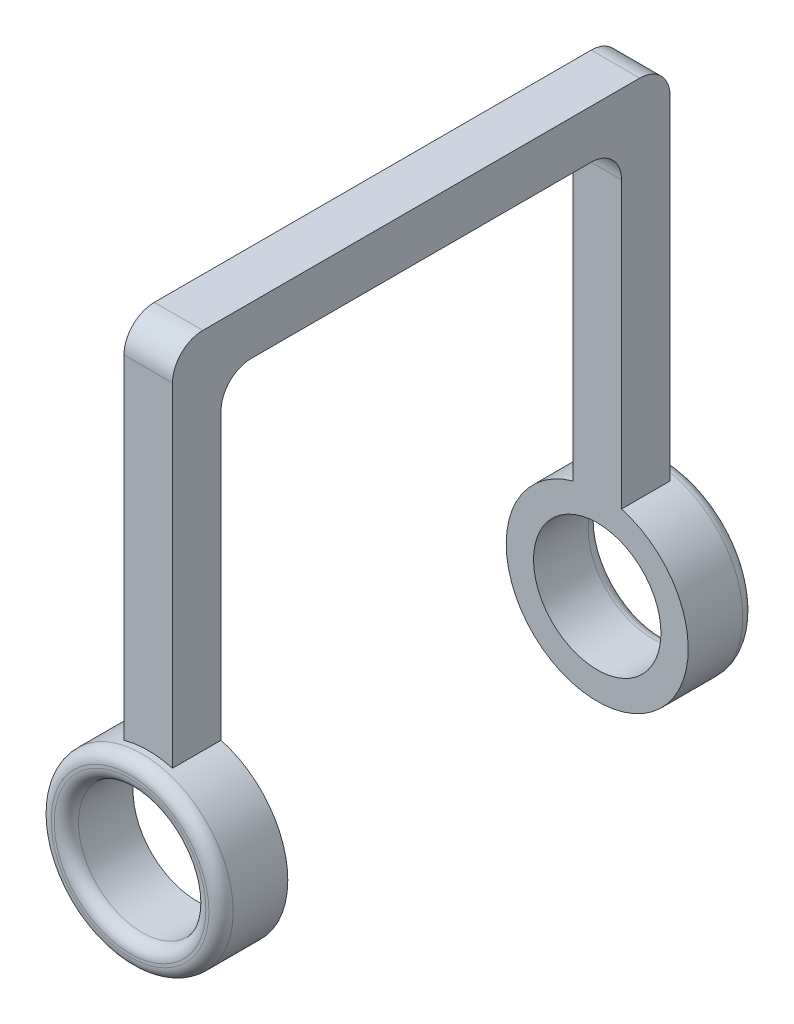
SolidWorks part; units mm, degrees
ref_plane "Front Plane" through (0, 0, 0) normal (0, 0, 1) x (1, 0, 0)
ref_plane "Top Plane" through (0, 0, 0) normal (0, 1, 0) x (1, 0, 0)
ref_plane "Right Plane" through (0, 0, 0) normal (1, 0, 0) x (0, 0, -1)
sketch "Sketch1" plane through (0, 0, 0) normal (0, 0, 1) x (1, 0, 0)
  line L0 (0, 0) -> (0, 44.4568) construction
  line L1 (-4, 14.4568) -> (4, 14.4568)
  line L2 (-4, 14.4568) -> (-4, 74.4568)
  line L3 (-4, 74.4568) -> (4, 74.4568)
  line L4 (4, 14.4568) -> (4, 74.4568)
  line L5 (-4, 14.4568) -> (4, 74.4568) construction
  line L6 (-4, 74.4568) -> (4, 14.4568) construction
  circle A0 centre (0, 0) radius 15
  circle A1 centre (0, 0) radius 10.5
  point P4 (0, 44.4568)
  point P9 (0, 0)
  dimension "D1" = 30
  dimension "D2" = 21
  dimension "D3" = 8
  dimension "D4" = 60
extrude "Boss-Extrude1" add sketch "Sketch1" against normal blind 82 contours L1 A0 A1 | A0 L4 L3 L2 | L1 A0 region at (0, 14.6744, 0) region at (0, 44.6383, 0) region at (0, 14.0364, 0)
ref_plane "Plane1" through (0, 0, -41) normal (0, 0, 1) x (1, 0, 0)
extrude "Boss-Extrude2" add sketch "Sketch1<3>" along normal blind 3 contours L1 A0 A1 | L1 A0 region at (0, 14.6744, 0) region at (0, 14.0364, 0)
sketch "Sketch1<3>" plane through (0, 0, 0) normal (0, 0, 1) x (1, 0, 0) same geometry as "Sketch1"
mirror "Mirror1" about plane through (0, 0, -41) normal (0, 0, 1) of "Boss-Extrude2"
sketch "Sketch2" plane through (-4, 0, 0) normal (-1, 0, 0) x (0, 0, 1)
  line L0 (-41, 74.4568) -> (-41, -15) construction
  line L1 (-82, 74.4568) -> (0, 74.4568) construction
  line L2 (-85, -15) -> (3, -15) construction
  line L3 (-82, 14.4568) -> (-82, 74.4568) construction
  line L4 (-74, -26.7788) -> (-8, -26.7788)
  line L5 (-74, -26.7788) -> (-74, 66.4568)
  line L6 (-74, 66.4568) -> (-8, 66.4568)
  line L7 (-8, -26.7788) -> (-8, 66.4568)
  line L8 (-74, -26.7788) -> (-8, 66.4568) construction
  line L9 (-74, 66.4568) -> (-8, -26.7788) construction
  point P6 (-41, 19.839)
  point P13 (-8, -26.7788)
  dimension "D1" = 8
  dimension "D2" = 8
extrude "Cut-Extrude1" cut sketch "Sketch2" against normal through all both and the other way through all
fillet "Fillet1" radius 5 4 edges at (0, 66.4568, -74) (0, 66.4568, -8) (0, 74.4568, 0) (0, 74.4568, -82)
fillet "Fillet2" radius 2 4 edges at (15, 0, 3) (10.5, 0, 3) (15, 0, -85) (10.5, 0, -85)
